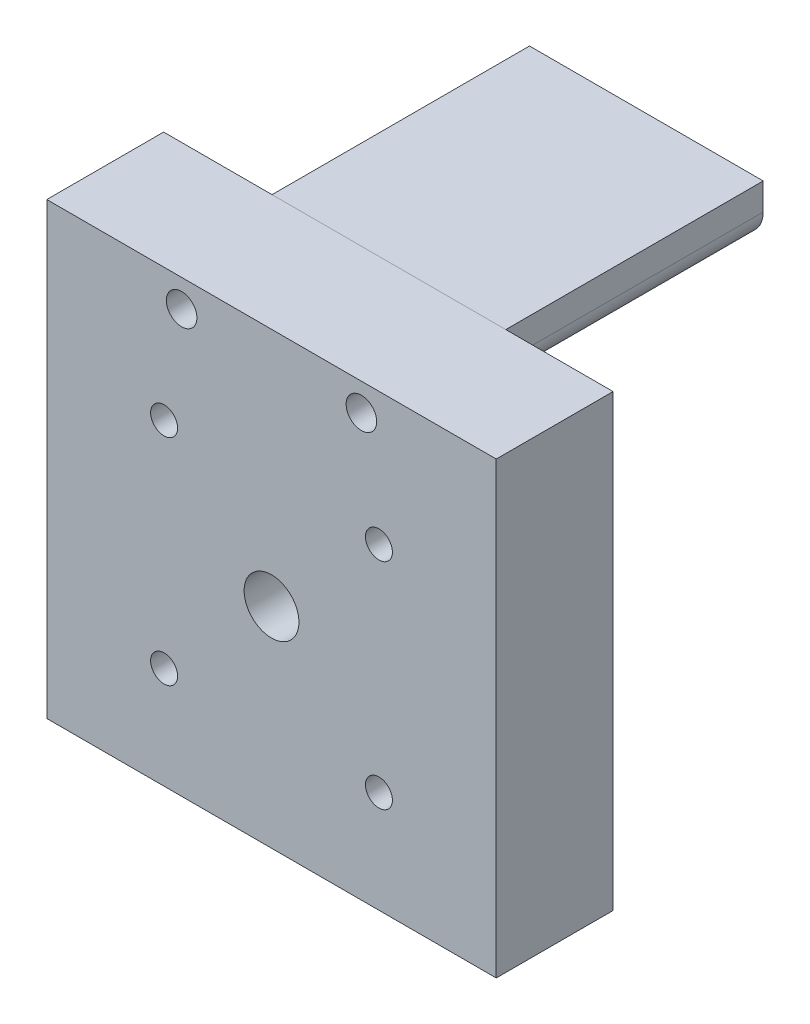
SolidWorks part; units mm, degrees
ref_plane "Front Plane" through (0, 0, 0) normal (0, 0, 1) x (1, 0, 0)
ref_plane "Top Plane" through (0, 0, 0) normal (0, 1, 0) x (1, 0, 0)
ref_plane "Right Plane" through (0, 0, 0) normal (1, 0, 0) x (0, 0, -1)
sketch "Sketch1" plane through (0, 0, 0) normal (0, 0, 1) x (1, 0, 0)
  line L1 (-13, 3) -> (13, 3)
  line L2 (-13, 3) -> (-13, -3)
  line L3 (-13, -3) -> (13, -3)
  line L4 (13, 3) -> (13, -3)
  line L5 (-13, 3) -> (13, -3) construction
  line L6 (-13, -3) -> (13, 3) construction
  point P0 (0, 0)
  dimension "D1" = 26
  dimension "D2" = 6
extrude "Boss-Extrude1" add sketch "Sketch1" along normal blind 28.7
sketch "Sketch4" plane through (0, 0, 0) normal (0, 0, -1) x (-1, 0, 0)
  line L0 (10, 0) -> (-15, 0)
  line L1 (10, 0) -> (0, 0)
  line L2 (0, 0) -> (0, -22)
  line L3 (13, 3) -> (13, -3) construction
  circle A0 centre (10, 0) radius 1.7
  circle A1 centre (-15, 0) radius 1.7
  dimension "D1" = 25
  dimension "D2" = 10
  dimension "D3" = 22
  dimension "D4" = 3
extrude "Cut-Extrude2" cut sketch "Sketch4" against normal blind 9 contours A0 | A1 region at (16.6519, 0, 0) region at (-10, 1.6519, 0)
sketch "Sketch8" plane through (0, 0, 28.7) normal (0, 0, 1) x (1, 0, 0)
  line L0 (-13, 0) -> (-10, 0)
  line L1 (-13, 3) -> (-13, -3) construction
  line L2 (-10, 0) -> (10, 0)
  line L3 (-10, 0) -> (0, 0)
  circle A0 centre (-10, 0) radius 1.7
  circle A1 centre (10, 0) radius 1.7
  dimension "D1" = 3
  dimension "D2" = 20
  dimension "D3" = 10
extrude "Cut-Extrude4" cut sketch "Sketch8" against normal through all contours A1 | L0 A0 L2 | L2 A0 L0 region at (-10, 0.7215, 28.7) region at (10, 1.6519, 28.7) region at (-10, -0.7215, 28.7)
fillet "Fillet2" radius 3 2 edges at (13, -3, 14.35) (-13, -3, 14.35)
sketch "Sketch9" plane through (0, 0, 0) normal (0, 0, -1) x (-1, 0, 0)
  line L0 (10, 0) -> (0, 0)
  line L1 (0, 0) -> (0, -23)
  circle A0 centre (0, -23) radius 22.5
  line M8 (-10, -3) -> (10, -3)
  arc M9 (10, -3) -> (13, 0) centre (10, 0) ccw
  dimension "D1" = 10
  dimension "D2" = 23
extrude "Cut-Extrude5" cut sketch "Sketch9" against normal blind 45 contours A0 M8 M9 | L1 A0 M8 | A0 L1 M9 M8 region at (-3.8952, -1.995, 0) region at (0.043, -23.2321, 0)
sketch "草图2" plane through (0, 0, 28.7) normal (0, 0, 1) x (1, 0, 0)
  line L0 (0, -16.8224) -> (0, -30.4889) construction
  line L1 (-25, 3.0593) -> (25, 3.0593)
  line L2 (-25, 3.0593) -> (-25, -46.9407)
  line L3 (-25, -46.9407) -> (25, -46.9407)
  line L4 (25, 3.0593) -> (25, -46.9407)
  line L5 (-5.7283, -23.6407) -> (5.0347, -23.6407)
  line L7 (-13, 3) -> (-13, 0) construction
  circle A0 centre (0, -23.6407) radius 3.05
  circle A1 centre (-11.95, -11.6907) radius 1.5
  circle A2 centre (11.95, -11.6907) radius 1.5
  circle A3 centre (11.95, -35.5907) radius 1.5
  circle A4 centre (-11.95, -35.5907) radius 1.5
  arc M9 (-10.282, -2.9867) -> (10.282, -2.9867) centre (0, -23) cw
  arc M10 (10.282, -2.9867) -> (13, 0) centre (10, 0) ccw
  line M11 (13, 0) -> (13, 3)
  line M12 (13, 3) -> (-13, 3)
  line M13 (-13, 3) -> (-13, 0)
  arc M14 (-13, 0) -> (-10.282, -2.9867) centre (-10, 0) ccw
  circle M15 centre (10, 0) radius 1.7
  circle M16 centre (-10, 0) radius 1.7
  dimension "D2" = 26.7
  dimension "D4" = 11.95
  dimension "D1" = 50
  dimension "D3" = 25
  dimension "D5" = 11.95
  dimension "D6" = 50
  dimension "D7" = 13
extrude "凸台-拉伸2" add sketch "草图2" along normal blind 13 contours M14 M9 M10 M11 M12 M13 M15 M16 | L4 L1 L2 L3 A2 A1 A0 A3 A4 region at (0, -14.6184, 28.7) region at (0, 0.7896, 28.7)
